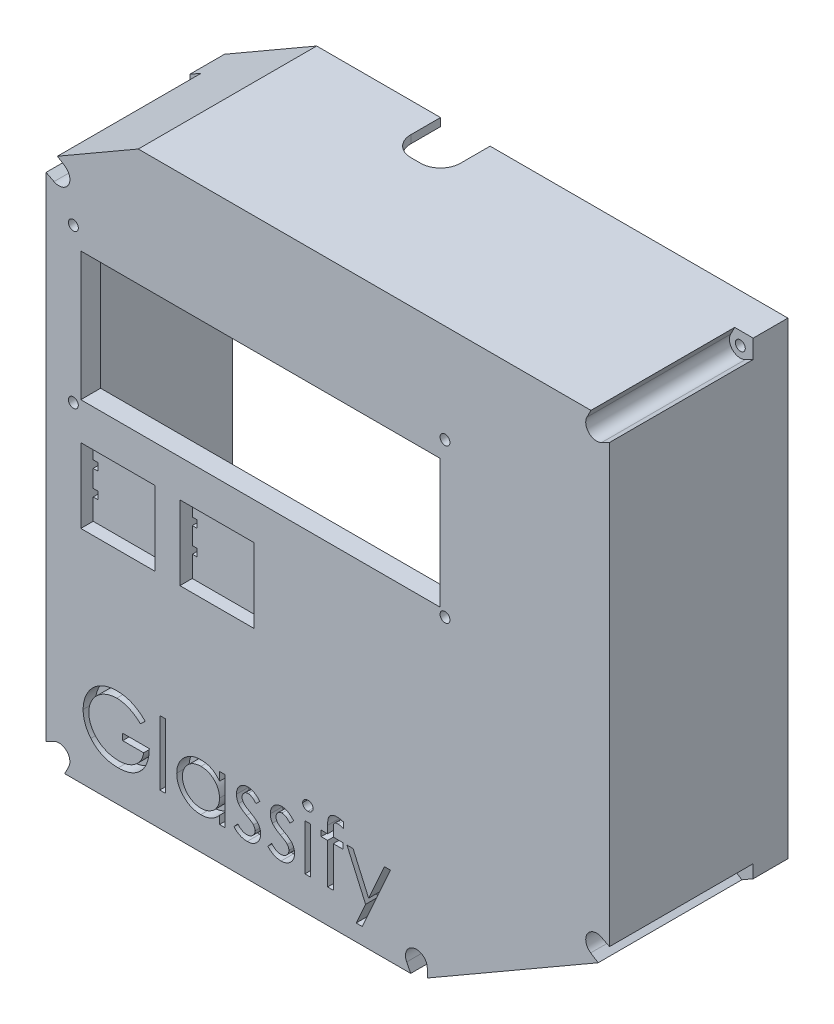
SolidWorks part; units mm, degrees
note: The reader was unsure of these and kept them because the rebuilt part matched: shared geometry of "Sketch8<4>".
ref_plane "Front Plane" through (0, 0, 0) normal (0, 0, 1) x (1, 0, 0)
ref_plane "Top Plane" through (0, 0, 0) normal (0, 1, 0) x (1, 0, 0)
ref_plane "Right Plane" through (0, 0, 0) normal (1, 0, 0) x (0, 0, -1)
sketch "Sketch1" plane through (0, 0, 0) normal (0, 0, 1) x (1, 0, 0)
  line L0 (-33.7504, 284.5362) -> (-31.8213, 285.65)
  line L1 (-31.8213, 285.65) -> (-29.5937, 285.65)
  line L6 (62.85, 287.25) -> (-32.25, 287.25)
  line L7 (62.85, 192.75) -> (62.85, 287.25)
  line L8 (24.5717, 170.65) -> (62.85, 192.75)
  line L9 (-50.85, 170.65) -> (24.5717, 170.65)
  line L10 (-50.85, 276.5113) -> (-50.85, 170.65)
  line L11 (-32.25, 287.25) -> (-50.85, 276.5113)
  line L18 (62.85, 287.25) -> (-32.25, 287.25)
  line L19 (62.85, 192.75) -> (62.85, 287.25)
  line L20 (24.5717, 170.65) -> (62.85, 192.75)
  line L21 (-50.85, 170.65) -> (24.5717, 170.65)
  line L22 (-50.85, 276.5113) -> (-50.85, 170.65)
  line L23 (-32.25, 287.25) -> (-50.85, 276.5113)
  line L24 (-49.25, 273.0506) -> (-49.25, 175.2096)
  line L25 (-33.7504, 284.5362) -> (-47.0529, 276.856)
  line L26 (58.2904, 285.65) -> (-29.5937, 285.65)
  line L27 (61.25, 196.2107) -> (61.25, 282.6904)
  line L28 (26.0721, 173.3638) -> (59.0529, 192.4053)
  line L29 (-46.2904, 172.25) -> (21.9154, 172.25)
  line L30 (-49.25, 273.0506) -> (-49.25, 175.2096)
  line L31 (-33.7504, 284.5362) -> (-47.0529, 276.856)
  line L32 (58.2904, 285.65) -> (-29.5937, 285.65)
  line L33 (61.25, 196.2107) -> (61.25, 282.6904)
  line L34 (26.0721, 173.3638) -> (59.0529, 192.4053)
  line L35 (-46.2904, 172.25) -> (21.9154, 172.25)
  circle A1 centre (-48.25, 173.25) radius 1
  circle A2 centre (-48.25, 173.25) radius 1
  circle A3 centre (-48.25, 275.0102) radius 1
  circle A4 centre (-48.25, 275.0102) radius 1
  circle A7 centre (60.25, 194.2511) radius 1
  circle A8 centre (60.25, 194.2511) radius 1
  circle A9 centre (60.25, 284.65) radius 1
  circle A10 centre (60.25, 284.65) radius 1
  circle A11 centre (23.875, 173.25) radius 1
  circle A12 centre (23.875, 173.25) radius 1
  arc A18 (-46.2904, 172.25) -> (-49.25, 175.2096) centre (-48.25, 173.25) ccw
  arc A19 (-49.25, 273.0506) -> (-47.0529, 276.856) centre (-48.25, 275.0102) ccw
  arc A20 (-33.7504, 284.5362) -> (-29.5937, 285.65) centre (-31.5533, 284.65) ccw
  arc A21 (58.2904, 285.65) -> (61.25, 282.6904) centre (60.25, 284.65) ccw
  arc A22 (61.25, 196.2107) -> (59.0529, 192.4053) centre (60.25, 194.2511) ccw
  arc A23 (26.0721, 173.3638) -> (21.9154, 172.25) centre (23.875, 173.25) ccw
  arc A24 (-46.2904, 172.25) -> (-49.25, 175.2096) centre (-48.25, 173.25) ccw
  arc A25 (-49.25, 273.0506) -> (-47.0529, 276.856) centre (-48.25, 275.0102) ccw
  arc A27 (58.2904, 285.65) -> (61.25, 282.6904) centre (60.25, 284.65) ccw
  arc A28 (61.25, 196.2107) -> (59.0529, 192.4053) centre (60.25, 194.2511) ccw
  arc A29 (26.0721, 173.3638) -> (21.9154, 172.25) centre (23.875, 173.25) ccw
  dimension "D1" = 0
  dimension "D2" = 0
  dimension "D3" = 0
  dimension "D5" = 0
  dimension "D6" = 0
  dimension "D7" = 0
  dimension "D8" = 0
extrude "Boss-Extrude1" add sketch "Sketch1" along normal blind 32
sketch "Sketch2" plane through (0, 0, 32) normal (0, 0, 1) x (1, 0, 0)
  line L0 (24.5717, 170.65) -> (62.85, 192.75) construction
  line L1 (-50.85, 170.65) -> (24.5717, 170.65) construction
  line L2 (-50.85, 276.5113) -> (-50.85, 170.65) construction
  line L3 (-32.25, 287.25) -> (-50.85, 276.5113) construction
  line L4 (62.85, 287.25) -> (-32.25, 287.25) construction
  line L5 (62.85, 192.75) -> (62.85, 287.25) construction
  line L6 (24.5717, 170.65) -> (62.85, 192.75)
  line L7 (-50.85, 170.65) -> (24.5717, 170.65)
  line L8 (-50.85, 276.5113) -> (-50.85, 170.65)
  line L9 (-32.25, 287.25) -> (-50.85, 276.5113)
  line L10 (62.85, 287.25) -> (-32.25, 287.25)
  line L11 (62.85, 192.75) -> (62.85, 287.25)
extrude "Boss-Extrude2" add sketch "Sketch2" along normal blind 4
sketch "Sketch3" plane through (0, 0, 36) normal (0, 0, 1) x (1, 0, 0)
  line L1 (-47.85, 269.8843) -> (32.15, 269.8843) construction
  line L2 (-47.85, 269.8843) -> (-47.85, 233.8843) construction
  line L3 (-47.85, 233.8843) -> (32.15, 233.8843) construction
  line L4 (32.15, 269.8843) -> (32.15, 233.8843) construction
  line L5 (-50.85, 170.65) -> (24.5717, 170.65) construction
  line L6 (-47.85, 228.65) -> (-2.85, 228.65) construction
  line L7 (-47.85, 228.65) -> (-47.85, 173.65) construction
  line L8 (-47.85, 173.65) -> (-2.85, 173.65) construction
  line L9 (-2.85, 228.65) -> (-2.85, 173.65) construction
  line L10 (-50.85, 276.5113) -> (-50.85, 170.65) construction
  dimension "D1" = 80
  dimension "D2" = 36
  dimension "D3" = 55
  dimension "D4" = 45
  dimension "D5" = 3
  dimension "D6" = 3
sketch "Sketch4" plane through (0, 0, 32) normal (0, 0, -1) x (-1, 0, 0)
  line L1 (-28.65, 263.6343) -> (43.85, 263.6343)
  line L2 (-28.65, 263.6343) -> (-28.65, 237.6343)
  line L3 (-28.65, 237.6343) -> (43.85, 237.6343)
  line L4 (43.85, 263.6343) -> (43.85, 237.6343)
  dimension "D1" = 26
  dimension "D2" = 72.5
  dimension "D3" = 6.25
  dimension "D4" = 3.5
extrude "Cut-Extrude1" cut sketch "Sketch4" against normal up to surface (4 mm away) up to face at (2.7203, 230.8435, 36)
sketch "Sketch5" plane through (0, 0, 32) normal (0, 0, -1) x (-1, 0, 0)
  line L0 (47.85, 269.8843) -> (47.85, 233.8843) construction
  line L1 (-32.15, 269.8843) -> (-32.15, 233.8843) construction
  line L2 (47.85, 269.8843) -> (-32.15, 269.8843) construction
  line L3 (47.85, 233.8843) -> (-32.15, 233.8843) construction
  line L4 (47.85, 228.65) -> (2.85, 228.65) construction
  line L5 (47.85, 228.65) -> (47.85, 173.65) construction
  line L6 (47.85, 173.65) -> (2.85, 173.65) construction
  line L7 (2.85, 228.65) -> (2.85, 173.65) construction
  line L8 (47.85, 228.65) -> (2.85, 228.65) construction
  line L9 (47.85, 228.65) -> (47.85, 173.65) construction
  line L10 (47.85, 173.65) -> (2.85, 173.65) construction
  line L11 (2.85, 228.65) -> (2.85, 173.65) construction
  line L13 (5.35, 226.15) -> (30.35, 226.15) construction
  line L14 (5.35, 226.15) -> (5.35, 224.15) construction
  line L15 (5.35, 224.15) -> (30.35, 224.15) construction
  line L16 (30.35, 226.15) -> (30.35, 224.15) construction
  circle A0 centre (45.35, 267.3843) radius 1
  circle A1 centre (45.35, 236.3843) radius 1
  circle A2 centre (-29.65, 267.3843) radius 1
  circle A3 centre (-29.65, 236.3843) radius 1
  dimension "D5" = 2
  dimension "D1" = 2.5
  dimension "D2" = 2.5
  dimension "D3" = 2.5
  dimension "D4" = 2.5
  dimension "D6" = 25
  dimension "D7" = 2
  dimension "D8" = 2.5
  dimension "D9" = 2.5
extrude "Cut-Extrude2" cut sketch "Sketch5" against normal up to surface (4 mm away) up to face at (-7.6, 250.6343, 36)
sketch "Sketch6" plane through (0, 0, 36) normal (0, 0, 1) x (1, 0, 0)
  line L0 (-50.85, 170.65) -> (24.5717, 170.65) construction
  line L2 (-50.85, 276.5113) -> (-50.85, 170.65) construction
  line L4 (-42.85, 173.65) -> (2.15, 173.65) construction
  line L5 (2.15, 228.65) -> (2.15, 173.65) construction
  line L6 (-42.85, 228.65) -> (2.15, 228.65) construction
  line L7 (-42.85, 228.65) -> (-42.85, 173.65) construction
  line L8 (-43.85, 172.65) -> (3.15, 172.65)
  line L9 (3.15, 229.65) -> (3.15, 172.65)
  line L10 (-43.85, 229.65) -> (3.15, 229.65)
  line L11 (-43.85, 229.65) -> (-43.85, 172.65)
  line L12 (-45.85, 231.65) -> (5.15, 231.65)
  line L13 (5.15, 231.65) -> (5.15, 170.65)
  line L14 (-45.85, 170.65) -> (5.15, 170.65)
  line L15 (-45.85, 231.65) -> (-45.85, 170.65)
  dimension "D3" = 45
  dimension "D4" = 55
  dimension "D5" = 5
  dimension "D1" = 1
  dimension "D2" = 2
fillet "Fillet2" radius 2.5 5 edges at (58.6944, 283.0944, 32) (23.3056, 175.375, 32) (58.3447, 195.3511, 32) (-46.6944, 174.8056, 32) (-46.3447, 273.9102, 32)
sketch "Sketch8" plane through (0, 0, 36) normal (0, 0, 1) x (1, 0, 0)
  line L0 (61.25, 196.2107) -> (62.85, 195.3942)
  line L1 (62.85, 192.75) -> (62.85, 287.25) construction
  line L2 (62.85, 195.3942) -> (62.85, 192.75)
  line L3 (62.85, 192.75) -> (60.5601, 191.4279)
  line L4 (24.5717, 170.65) -> (62.85, 192.75) construction
  line L5 (60.5601, 191.4279) -> (59.0529, 192.4053)
  line L6 (26.0721, 173.3638) -> (26.165, 171.5699)
  line L7 (26.165, 171.5699) -> (24.5717, 170.65)
  line L8 (24.5717, 170.65) -> (22.7319, 170.65)
  line L9 (-50.85, 170.65) -> (24.5717, 170.65) construction
  line L10 (22.7319, 170.65) -> (21.9154, 172.25)
  line L11 (-46.2904, 172.25) -> (-47.1069, 170.65)
  line L18 (-46.2904, 172.25) -> (21.9154, 172.25)
  line L19 (-49.25, 273.0506) -> (-49.25, 175.2096)
  line L20 (-33.7504, 284.5362) -> (-47.0529, 276.856)
  line L21 (58.2904, 285.65) -> (-29.5937, 285.65)
  line L22 (61.25, 196.2107) -> (61.25, 282.6904)
  line L23 (26.0721, 173.3638) -> (59.0529, 192.4053)
  line L30 (-50.85, 170.65) -> (24.5717, 170.65) construction
  line L31 (-47.1069, 170.65) -> (-50.85, 170.65)
  line L32 (-50.85, 170.65) -> (-50.85, 174.3931)
  line L33 (-50.85, 276.5113) -> (-50.85, 170.65) construction
  line L34 (-50.85, 174.3931) -> (-49.25, 175.2096)
  line L35 (-47.0529, 276.856) -> (-48.5601, 277.8334)
  line L36 (-32.25, 287.25) -> (-50.85, 276.5113) construction
  line L37 (-48.5601, 277.8334) -> (-50.85, 276.5113)
  line L38 (-50.85, 276.5113) -> (-50.85, 273.8671)
  line L39 (-50.85, 276.5113) -> (-50.85, 170.65) construction
  line L40 (-50.85, 273.8671) -> (-49.25, 273.0506)
  line L42 (62.85, 287.25) -> (-32.25, 287.25) construction
  line L47 (58.2904, 285.65) -> (59.1069, 287.25)
  line L48 (59.1069, 287.25) -> (62.85, 287.25)
  line L49 (62.85, 287.25) -> (62.85, 283.5069)
  line L50 (62.85, 283.5069) -> (61.25, 282.6904)
  line L59 (-29.5937, 285.65) -> (-31.8213, 285.65)
  line L61 (-31.8213, 285.65) -> (-33.7504, 284.5362)
  circle A1 centre (-48.25, 275.0102) radius 1
  circle A2 centre (-48.25, 275.0102) radius 1
  circle A3 centre (-48.25, 173.25) radius 1
  circle A4 centre (-48.25, 173.25) radius 1
  circle A5 centre (23.875, 173.25) radius 1
  circle A6 centre (23.875, 173.25) radius 1
  circle A7 centre (60.25, 284.65) radius 1
  circle A8 centre (60.25, 284.65) radius 1
  circle A9 centre (60.25, 194.2511) radius 1
  circle A10 centre (60.25, 194.2511) radius 1
  arc A18 (-46.2904, 172.25) -> (-49.25, 175.2096) centre (-48.25, 173.25) ccw
  arc A19 (-49.25, 273.0506) -> (-47.0529, 276.856) centre (-48.25, 275.0102) ccw
  arc A21 (58.2904, 285.65) -> (61.25, 282.6904) centre (60.25, 284.65) ccw
  arc A22 (61.25, 196.2107) -> (59.0529, 192.4053) centre (60.25, 194.2511) ccw
  arc A23 (26.0721, 173.3638) -> (21.9154, 172.25) centre (23.875, 173.25) ccw
  arc A24 (-46.2904, 172.25) -> (-49.25, 175.2096) centre (-48.25, 173.25) ccw
  arc A25 (-49.25, 273.0506) -> (-47.0529, 276.856) centre (-48.25, 275.0102) ccw
  arc A27 (58.2904, 285.65) -> (61.25, 282.6904) centre (60.25, 284.65) ccw
  arc A28 (61.25, 196.2107) -> (59.0529, 192.4053) centre (60.25, 194.2511) ccw
  arc A29 (26.0721, 173.3638) -> (21.9154, 172.25) centre (23.875, 173.25) ccw
  text T0 "Glassify" font "Century Gothic" height in points 48
  point P1 (0, 0)
  point P80 (0, 0)
  line M3 (-50.85, 170.65) -> (24.5717, 170.65)
  line M4 (24.5717, 170.65) -> (62.85, 192.75)
  line M5 (62.85, 192.75) -> (62.85, 287.25)
  line M7 (-32.25, 287.25) -> (-50.85, 276.5113)
  line M8 (-50.85, 276.5113) -> (-50.85, 170.65)
  dimension "D1" = 0
  dimension "D2" = 0
  dimension "D4" = 0
  dimension "D5" = 0
  dimension "D6" = 0
  dimension "D8" = 0
extrude "Cut-Extrude4" cut sketch "Sketch8" against normal offset from surface (29 mm away) 7 contours L6 A29 L10 A6 M3 M4 | L40 A25 L35 A2 M7 M8 | L0 A28 L5 A10 M4 M5 | L31 L32 L34 A24 L11 | L49 L50 A27 L47 L48 up to face at (-47.25, 275.0102, 0)
extrude "Cut-Extrude11" cut sketch "Sketch8<4>" against normal blind 2.5
sketch "Sketch8<4>" plane through (0, 0, 36) normal (0, 0, 1) x (1, 0, 0) same geometry as "Sketch8"
sketch "Sketch9" plane through (0, 0, 36) normal (0, 0, 1) x (1, 0, 0)
  line L1 (-43.85, 230.1343) -> (-28.85, 230.1343)
  line L2 (-43.85, 230.1343) -> (-43.85, 215.1343)
  line L3 (-43.85, 215.1343) -> (-28.85, 215.1343)
  line L4 (-28.85, 230.1343) -> (-28.85, 215.1343)
  line L5 (-23.85, 230.1343) -> (-8.85, 230.1343)
  line L6 (-23.85, 230.1343) -> (-23.85, 215.1343)
  line L7 (-23.85, 215.1343) -> (-8.85, 215.1343)
  line L8 (-8.85, 230.1343) -> (-8.85, 215.1343)
  line L11 (-43.85, 237.6343) -> (-43.85, 263.6343) construction
  line L12 (28.65, 237.6343) -> (-43.85, 237.6343) construction
  point P4 (-22.6569, 210.3352)
  point P5 (-26.6006, 227.5)
  point P6 (0, 0)
  point P11 (-20.0157, 208.75)
  point P12 (-16, 212.5)
  point P15 (-36, 224.2164)
  dimension "D1" = 15
  dimension "D2" = 15
  dimension "D3" = 15
  dimension "D4" = 15
  dimension "D5" = 5
  dimension "D6" = 7.5
extrude "Cut-Extrude6" cut sketch "Sketch9" against normal blind 2.5
sketch "Sketch10" plane through (0, 0, 33.5) normal (0, 0, 1) x (1, 0, 0)
  line L0 (-36.35, 230.1343) -> (-36.35, 215.1343) construction
  line L1 (-28.85, 230.1343) -> (-43.85, 230.1343) construction
  line L2 (-43.85, 215.1343) -> (-28.85, 215.1343) construction
  line L3 (-16.35, 230.1343) -> (-16.35, 215.1343) construction
  line L4 (-8.85, 230.1343) -> (-23.85, 230.1343) construction
  line L5 (-23.85, 215.1343) -> (-8.85, 215.1343) construction
  line L6 (-28.85, 222.6343) -> (-43.85, 222.6343) construction
  line L7 (-43.85, 225.8843) -> (-42.85, 225.8843)
  line L8 (-43.85, 225.8843) -> (-43.85, 224.3843)
  line L9 (-43.85, 224.3843) -> (-42.85, 224.3843)
  line L10 (-42.85, 225.8843) -> (-42.85, 224.3843)
  line L11 (-28.85, 215.1343) -> (-28.85, 230.1343) construction
  line L12 (-43.85, 229.65) -> (-43.85, 172.65) construction
  line L13 (-26.35, 232.815) -> (-26.35, 212.4829) construction
  line L14 (-43.85, 219.3843) -> (-43.85, 220.8843)
  line L15 (-43.85, 219.3843) -> (-42.85, 219.3843)
  line L16 (-42.85, 219.3843) -> (-42.85, 220.8843)
  line L17 (-43.85, 220.8843) -> (-42.85, 220.8843)
  line L18 (-28.85, 220.8843) -> (-29.85, 220.8843)
  line L19 (-29.85, 219.3843) -> (-29.85, 220.8843)
  line L20 (-28.85, 219.3843) -> (-29.85, 219.3843)
  line L21 (-28.85, 219.3843) -> (-28.85, 220.8843)
  line L22 (-28.85, 224.3843) -> (-29.85, 224.3843)
  line L23 (-28.85, 225.8843) -> (-28.85, 224.3843)
  line L24 (-28.85, 225.8843) -> (-29.85, 225.8843)
  line L25 (-29.85, 225.8843) -> (-29.85, 224.3843)
  line L26 (-22.85, 225.8843) -> (-22.85, 224.3843)
  line L27 (-23.85, 225.8843) -> (-22.85, 225.8843)
  line L28 (-23.85, 225.8843) -> (-23.85, 224.3843)
  line L29 (-23.85, 224.3843) -> (-22.85, 224.3843)
  line L30 (-23.85, 219.3843) -> (-23.85, 220.8843)
  line L31 (-23.85, 219.3843) -> (-22.85, 219.3843)
  line L32 (-22.85, 219.3843) -> (-22.85, 220.8843)
  line L33 (-23.85, 220.8843) -> (-22.85, 220.8843)
  line L34 (-8.85, 220.8843) -> (-9.85, 220.8843)
  line L35 (-9.85, 219.3843) -> (-9.85, 220.8843)
  line L36 (-8.85, 219.3843) -> (-9.85, 219.3843)
  line L37 (-8.85, 219.3843) -> (-8.85, 220.8843)
  line L38 (-9.85, 225.8843) -> (-9.85, 224.3843)
  line L39 (-8.85, 224.3843) -> (-9.85, 224.3843)
  line L40 (-8.85, 225.8843) -> (-8.85, 224.3843)
  line L41 (-8.85, 225.8843) -> (-9.85, 225.8843)
  point P22 (-43.85, 225.1343)
  point P23 (-43.35, 225.8843)
  dimension "D1" = 1.5
  dimension "D2" = 1
  dimension "D3" = 2.5
  dimension "D4" = 7
  dimension "D5" = 2.5
extrude "Cut-Extrude7" cut sketch "Sketch10" against normal through all both and the other way through all
sketch "Sketch11" plane through (-50.85, 0, 0) normal (-1, 0, 0) x (0, 0, 1)
  line L0 (0, 170.65) -> (0, 198.65) construction
  line L1 (0, 276.5113) -> (0, 170.65) construction
  line L2 (0, 205.65) -> (0, 191.65)
  line L3 (0, 191.65) -> (15, 191.65)
  line L4 (15, 205.65) -> (0, 205.65)
  arc A0 (15, 191.65) -> (15, 205.65) centre (15, 198.65) ccw
  point P10 (9.8057, 204.3958)
  point P11 (0, 193.4282)
  point P12 (0, 0)
  point P13 (0, 0)
  point P14 (15.1128, 191.65)
  dimension "D2" = 7
  dimension "D1" = 28
  dimension "D3" = 15
extrude "Cut-Extrude8" cut sketch "Sketch11" against normal up to next (1.6 mm away) and the other way through all
sketch "Sketch12" plane through (0, 170.65, 0) normal (0, -1, 0) x (1, 0, 0)
  line L0 (-43.35, 0) -> (-43.35, 5)
  line L1 (-50.85, 0) -> (24.5717, 0) construction
  line L2 (-38.35, 10) -> (-28.35, 10)
  line L3 (-23.35, 5) -> (-23.35, 0)
  line L4 (-23.35, 0) -> (-43.35, 0)
  line L5 (-50.85, 7) -> (-50.85, 0) construction
  arc A0 (-28.35, 10) -> (-23.35, 5) centre (-28.35, 5) cw
  arc A1 (-43.35, 5) -> (-38.35, 10) centre (-38.35, 5) cw
  dimension "D4" = 5
  dimension "D1" = 10
  dimension "D2" = 20
  dimension "D3" = 7.5
extrude "Cut-Extrude9" cut sketch "Sketch12" against normal up to next (1.6 mm away)
sketch "Sketch13" plane through (0, 287.25, 0) normal (0, 1, 0) x (1, 0, 0)
  line L0 (2.75, 0) -> (2.75, -6)
  line L1 (62.85, 0) -> (-32.25, 0) construction
  line L2 (-1.25, -10) -> (-3.25, -10)
  line L3 (-7.25, -6) -> (-7.25, 0)
  line L4 (-7.25, 0) -> (2.75, 0)
  line L5 (-32.25, -36) -> (-32.25, 0) construction
  arc A0 (2.75, -6) -> (-1.25, -10) centre (-1.25, -6) cw
  arc A1 (-3.25, -10) -> (-7.25, -6) centre (-3.25, -6) cw
  point P6 (-2.25, -10)
  point P14 (-7.25, -10)
  dimension "D4" = 4
  dimension "D1" = 10
  dimension "D2" = 10
  dimension "D3" = 30
extrude "Cut-Extrude10" cut sketch "Sketch13" against normal up to next (1.6 mm away)
sketch "Sketch14" plane through (0, 0, 36) normal (0, 0, 1) x (1, 0, 0)
  circle A0 centre (23.875, 173.25) radius 1 construction
  circle A1 centre (60.25, 194.2511) radius 1 construction
  circle A2 centre (-48.25, 275.0102) radius 1 construction
  circle A3 centre (23.875, 173.25) radius 1
  circle A4 centre (60.25, 194.2511) radius 1
  circle A5 centre (-48.25, 275.0102) radius 1
extrude "Cut-Extrude12" cut sketch "Sketch14" against normal through all both and the other way through all
